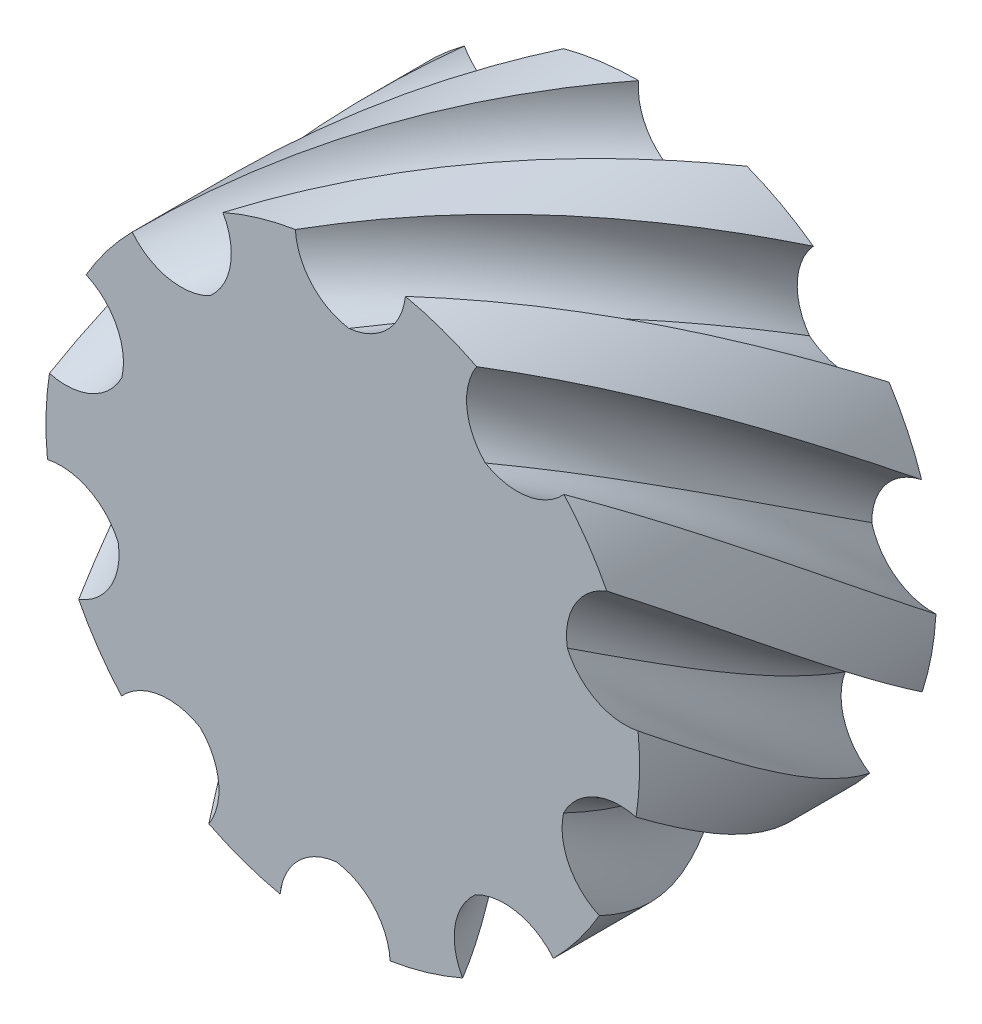
SolidWorks part; units mm, degrees
ref_plane "Front Plane" through (0, 0, 0) normal (0, 0, 1) x (1, 0, 0)
ref_plane "Top Plane" through (0, 0, 0) normal (0, 1, 0) x (1, 0, 0)
ref_plane "Right Plane" through (0, 0, 0) normal (1, 0, 0) x (0, 0, -1)
sketch "Sketch1" plane through (0, 0, 0) normal (0, 0, 1) x (1, 0, 0)
  circle A0 centre (0, 0) radius 4 construction
  circle A1 centre (0, 0) radius 4.8 construction
  circle A2 centre (0, 0) radius 5
extrude "Extrude1" add sketch "Sketch1" along normal blind 5
sketch "Sketch2" plane through (0, 0, 5) normal (0, 0, 1) x (1, 0, 0)
  line L0 (0, 5) -> (0.9972, 4.637) construction
  line L1 (1.0553, 4.8874) -> (1.5875, 6.35)
  line L2 (1.5875, 6.35) -> (-1.5875, 6.35)
  line L3 (0.6677, 12.7401) -> (0, 0) construction
  line L4 (0, 0) -> (9.525, 0) construction
  line L5 (0, 5) -> (3.7514, 5) construction
  line L6 (-1.5875, 6.35) -> (-0.798, 4.9359)
  circle A0 centre (0, 0) radius 5 construction
  circle A1 centre (0, 0) radius 4.8 construction
  circle A2 centre (0, 0) radius 4 construction
  circle A3 centre (0, 5) radius 1.0612 construction
  circle A4 centre (0.1994, 4.9274) radius 0.849 construction
  circle A5 centre (0.2617, 4.9931) radius 1.0612 construction
  arc A6 (0.1033, 3.9438) -> (1.0553, 4.8874) centre (0, 5) ccw
  arc A7 (0.1033, 3.9438) -> (-0.798, 4.9359) centre (0.2617, 4.9931) cw
  point P5 (0, 5)
  point P8 (0.9972, 4.637)
  point P9 (0.1994, 4.9274)
  point P14 (0.2617, 4.9931)
  point P19 (0.3163, 3.9875)
  point P20 (-0.1084, 3.9985)
  point P21 (0.1033, 3.9438)
  dimension "D1" = 10
  dimension "D2" = 9.6
  dimension "D3" = 8
  dimension "D4" = 20
  dimension "D5" = 0.849
  dimension "D6" = 2.1225
  dimension "D7" = 87
  dimension "RO2" = 2.1225
sketch "Sketch4" plane through (0, 0, 5) normal (0, 0, 1) x (1, 0, 0)
  circle A0 centre (0, 0) radius 5
curve "Helix/Spiral1" pitch 40 height 8 radius 5 centre (0, 0, 5) axis (0, 0, -1) start towards (0, 1, 0)
sweep "Cut-Sweep1" cut profiles "Sketch2" path "Helix/Spiral1"
pattern_circular "CirPattern1" count 10 over 360 about axis through (0, 0, 5) along (0, 0, 1) of "Cut-Sweep1"
equation "\"D6@Sketch2\" = \"RO2\""
